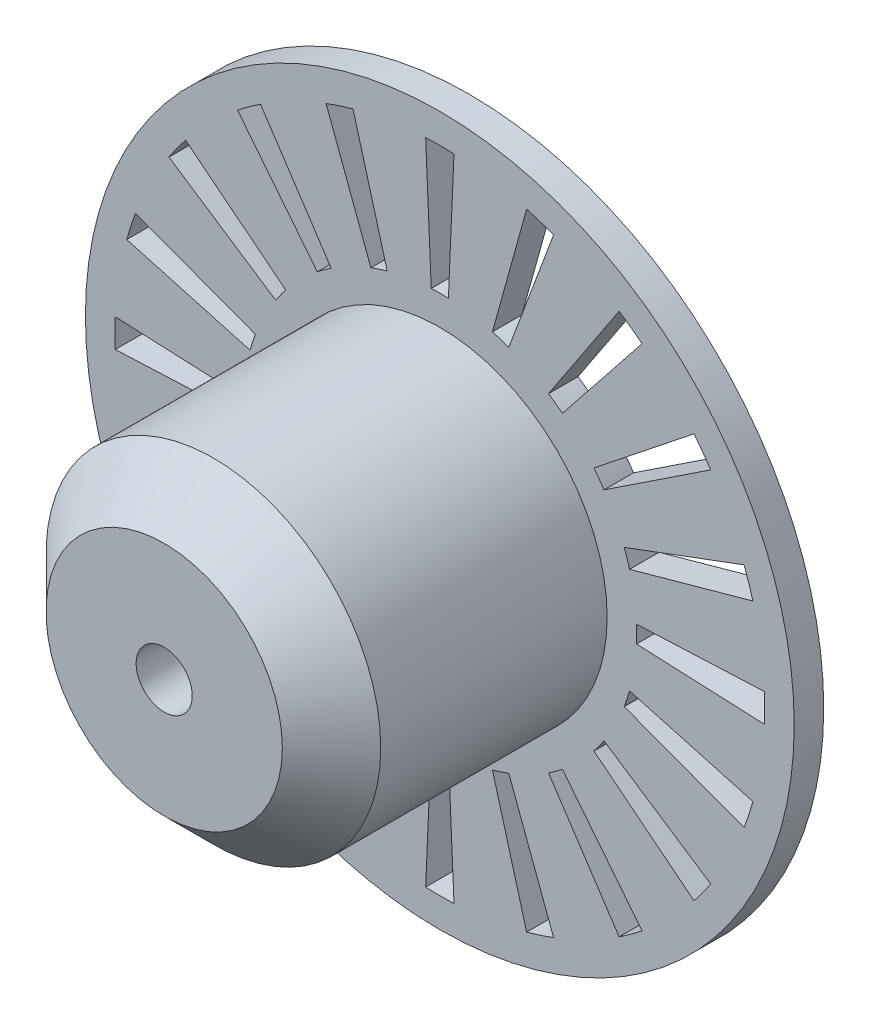
SolidWorks part; units mm, degrees
ref_plane "Plano frontal" through (0, 0, 0) normal (0, 0, 1) x (1, 0, 0)
ref_plane "Plano superior" through (0, 0, 0) normal (0, 1, 0) x (1, 0, 0)
ref_plane "Plano direito" through (0, 0, 0) normal (1, 0, 0) x (0, 0, -1)
sketch "Esboço1" plane through (0, 0, 0) normal (0, 0, 1) x (1, 0, 0)
  circle A0 centre (0, 0) radius 18
  dimension "D2" = 36
extrude "Ressalto-extrusão1" add sketch "Esboço1" along normal blind 1.5
sketch "Esboço3" plane through (0, 0, 1.5) normal (0, 0, 1) x (1, 0, 0)
  circle A1 centre (0, 0) radius 8.5
  dimension "D2" = 17
extrude "Ressalto-extrusão2" add sketch "Esboço3" along normal blind 14
sketch "Esboço4" plane through (0, 0, 1.5) normal (0, 0, 1) x (1, 0, 0)
  line L1 (-0.8, 7.2) -> (0.8, 7.2)
  line L2 (-0.8, 7.2) -> (-0.8, 4.2)
  line L3 (-0.8, 4.2) -> (0.8, 4.2)
  line L4 (0.8, 7.2) -> (0.8, 4.2)
  dimension "D1" = 0.8
  dimension "D2" = 0.8
  dimension "D3" = 4.2
  dimension "D4" = 3
extrude "Ressalto-extrusão3" add sketch "Esboço4" along normal blind 1.5
sketch "Esboço5" plane through (0, 0, 1.5) normal (0, 0, 1) x (1, 0, 0)
  line L0 (0, 0) -> (0, 18) construction
  line L5 (-0.4362, 9.9905) -> (-0.7197, 16.4843)
  line L6 (0.4362, 9.9905) -> (0.7197, 16.4843)
  circle A0 centre (0, 0) radius 18 construction
  arc A1 (0.7197, 16.4843) -> (-0.7197, 16.4843) centre (0, 0) ccw
  arc A2 (0.4362, 9.9905) -> (-0.4362, 9.9905) centre (0, 0) ccw
  dimension "D3" = 33
  dimension "D4" = 20
  dimension "D1" = 2.5
  dimension "D2" = 2.5
extrude "Corte-extrusão1" cut sketch "Esboço5" against normal through all
pattern_circular "PadrãoCircular1" count 20 over 360 about axis through (0, 0, 1.5) along (0, 0, -1) of "Corte-extrusão1" reverse direction yes
sketch "Esboço7" plane through (0, 0, 15.5) normal (0, 0, 1) x (1, 0, 0)
  circle A0 centre (0, 0) radius 1.425
  dimension "D1" = 2.85
extrude "Corte-extrusão2" cut sketch "Esboço7" against normal through all
chamfer "Chanfro1" distance 2.5 angle 45 1 edges at (8.5, 0, 15.5)
sketch "Esboço8" plane through (0, 0, 0) normal (0, 0, -1) x (-1, 0, 0)
  circle A0 centre (0, 0) radius 1.925
  dimension "D1" = 3.85
extrude "Corte-extrusão3" cut sketch "Esboço8" against normal blind 5.5
chamfer "Chanfro2" distance 0.5 angle 45 1 edges at (-1.925, 0, 0)
